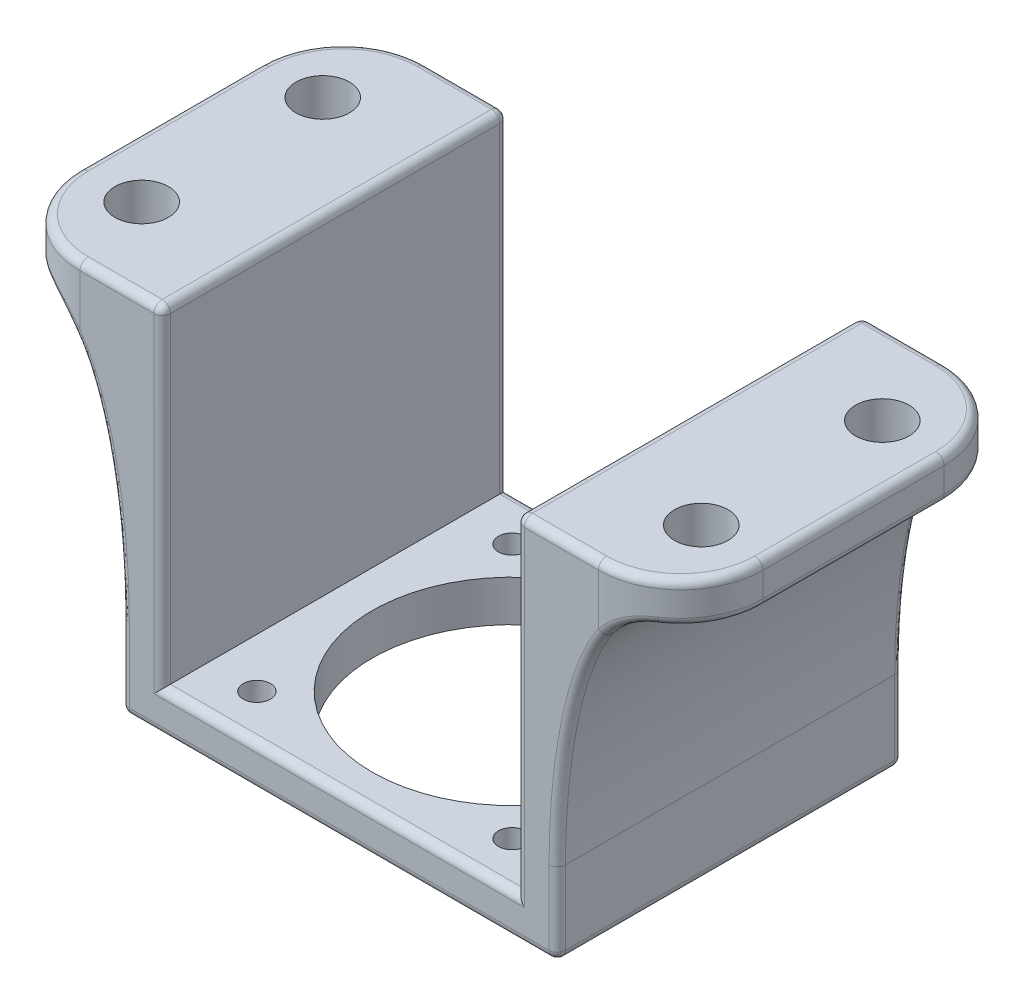
SolidWorks part; units mm, degrees
ref_plane "Płaszczyzna przednia" through (0, 0, 0) normal (0, 0, 1) x (1, 0, 0)
ref_plane "Płaszczyzna górna" through (0, 0, 0) normal (0, 1, 0) x (1, 0, 0)
ref_plane "Płaszczyzna prawa" through (0, 0, 0) normal (1, 0, 0) x (0, 0, -1)
sketch "Szkic1" plane through (0, 0, 0) normal (0, 0, 1) x (1, 0, 0)
  line L0 (-41.5, 40) -> (-21.5, 40)
  line L1 (-21.5, 40) -> (-21.5, 0)
  line L2 (-21.5, 0) -> (0, 0)
  line L3 (-41.5, 35) -> (-26.5, 35)
  line L4 (-26.5, 35) -> (-26.5, -5)
  line L5 (-26.5, -5) -> (0, -5)
  line L6 (-41.5, 40) -> (-41.5, 35)
  line L7 (0, 0) -> (0, -5)
  dimension "D1" = 21.5
  dimension "D2" = 40
  dimension "D3" = 20
  dimension "D4" = 5
extrude "Dodanie-wyciągnięcie1" add sketch "Szkic1" along normal mid plane 42
mirror "Lustro1" about plane through (0, 0, 21) normal (-1, 0, 0) of "Dodanie-wyciągnięcie1"
sketch "Szkic2" plane through (0, -5, 0) normal (0, -1, 0) x (-1, 0, 0)
  arc A0 (0, 16.5) -> (0, -16.5) centre (0, 0) ccw construction
  circle A1 centre (0, 0) radius 16.5 construction
  circle A2 centre (0, 0) radius 17
  dimension "D1" = 0.5
extrude "Wytnij-wyciągnięcie1" cut sketch "Szkic2" against normal up to surface (5 mm away) up to face at (0, 0, 0)
sketch "Szkic3" plane through (0, -5, 0) normal (0, -1, 0) x (-1, 0, 0)
  arc A0 (-15.5, 16.75) -> (-15.5, 14.25) centre (-15.5, 15.5) ccw construction
  arc A1 (-15.5, -14.25) -> (-15.5, -16.75) centre (-15.5, -15.5) ccw construction
  arc A2 (15.5, 16.75) -> (15.5, 14.25) centre (15.5, 15.5) ccw construction
  arc A3 (15.5, -14.25) -> (15.5, -16.75) centre (15.5, -15.5) ccw construction
  arc A4 (-15.5, 16.75) -> (-15.5, 14.25) centre (-15.5, 15.5) ccw
  arc A5 (-15.5, -14.25) -> (-15.5, -16.75) centre (-15.5, -15.5) ccw
  arc A6 (15.5, 16.75) -> (15.5, 14.25) centre (15.5, 15.5) ccw
  arc A7 (15.5, -14.25) -> (15.5, -16.75) centre (15.5, -15.5) ccw
hole_wizard "Otwory ustalające Ø3.0mm1" positions "Szkic4" profile "Szkic5" hole size "Ø3.0" standard "Ansi Metric"
sketch "Szkic4" plane through (0, -5, 0) normal (0, -1, 0) x (-1, 0, 0)
  point P0 (15.5, -15.5)
  point P3 (-15.5, -15.5)
  point P6 (15.5, 15.5)
  point P9 (-15.5, 15.5)
sketch "Szkic5" plane through (-15.5, -5, 15.5) normal (1, 0, 0) x (0, 0, -1)
  line L0 (0, 0) -> (0, 5.9914)
  line L1 (0, 5.9914) -> (1.65, 5)
  line L2 (1.65, 5) -> (1.65, 0)
  line L5 (1.65, 0) -> (0, 0)
  line L10 (0, 5.9914) -> (-1.65, 5) construction
  line L11 (0, -6.35) -> (0, 107.95) construction
  dimension "Średnica otworu" = 3.3
  dimension "Głębokość otworu" = 5
  dimension "Kąt wiertła" = 118
hole_wizard "Pogłębienie stożkowe pod M5 wkręt do części metalowych z łbem soczewkowym1" positions "Szkic6" profile "Szkic7" countersink size "M5" standard "Ansi Metric"
sketch "Szkic6" plane through (0, 56, -267.5) normal (0, 1, 0) x (0, 0, -1)
  line L1 (-288.5, -41.5) -> (-246.5, -41.5)
  line L3 (-288.5, 41.5) -> (-246.5, 41.5)
  point P0 (-256.5, -34)
  point P3 (-256.5, 34)
  point P5 (-278.5, 34)
  point P7 (-278.5, -34)
sketch "Szkic7" plane through (34, 56, -11) normal (1, 0, 0) x (0, 0, 1)
  line L0 (0, 0) -> (0, 62.6524)
  line L1 (0, 62.6524) -> (2.75, 61)
  line L2 (2.75, 61) -> (2.75, 2.45)
  line L3 (2.75, 2.45) -> (5.2, 0)
  line L4 (5.2, 0) -> (0, 0)
  line L5 (-2.75, 2.45) -> (-5.2, 0) construction
  line L6 (0, 62.6524) -> (-2.75, 61) construction
  line L7 (0, -6.35) -> (0, 107.95) construction
  dimension "Średnica otworu" = 5.5
  dimension "Głębokośc otworu" = 61
  dimension "Średnica zewnętrznego pogłębienia stożkowego" = 10.4
  dimension "Kąt zewnętrznego pogłębienia stożkowego" = 90
  dimension "Kąt wiertła" = 118
fillet "Zaokrąglenie1" radius 10 2 edges at (-26.5, 35, 0) (26.5, 35, 0) second distance 30 first distance on face at (-36.75, 35, -11) first distance on face at (36.75, 35, -11)
hole_wizard "Otwory ustalające Ø6.0mm1" positions "Szkic9" profile "Szkic11" hole size "Ø6.0" standard "Ansi Metric" end condition through all
sketch "Szkic9" plane through (0, 40, 0) normal (0, 1, 0) x (1, 0, 0)
  point P0 (34, -11)
  point P3 (34, 11)
  point P6 (-34, -11)
  point P9 (-34, 11)
sketch "Szkic11" plane through (34, 40, 11) normal (1, 0, 0) x (0, 0, 1)
  line L0 (0, 0) -> (0, 45)
  line L1 (0, 45) -> (3.25, 45)
  line L2 (3.25, 45) -> (3.25, 0)
  line L5 (3.25, 0) -> (0, 0)
  line L11 (0, -6.35) -> (0, 107.95) construction
  dimension "Średnica otworu na wylot" = 6.5
  dimension "Głębokość otworu na wylot" = 45
fillet "Zaokrąglenie2" radius 10 4 edges at (-41.5, 37.5, 21) (-41.5, 37.5, -21) (41.5, 37.5, 21) (41.5, 37.5, -21)
fillet "Zaokrąglenie3" radius 1 40 edges at (21.5, 40, 0) (-21.5, 40, 0) (-26.5, -5, 0) (26.5, -5, 0) (26.5, 40, -21) (21.5, 20, -21) (0, 0, -21) (-21.5, 20, -21) (-26.5, 40, -21) (-38.5711, 40, -18.0711) (-41.5, 40, 0) (-38.5711, 40, 18.0711) (-26.5, 40, 21) (-21.5, 20, 21) (0, 0, 21) (21.5, 20, 21) (26.5, 40, 21) (38.5711, 40, 18.0711) (41.5, 40, 0) (38.5711, 40, -18.0711) (41.5, 35, 0) (34.2168, 34.2076, 20.6239) (0, -5, 21) (-34.5303, 34.4123, 20.5298) (-41.5, 35, 0) (-34.2168, 34.2076, -20.6239) (0, -5, -21) (34.3803, 34.3183, -20.5762)
